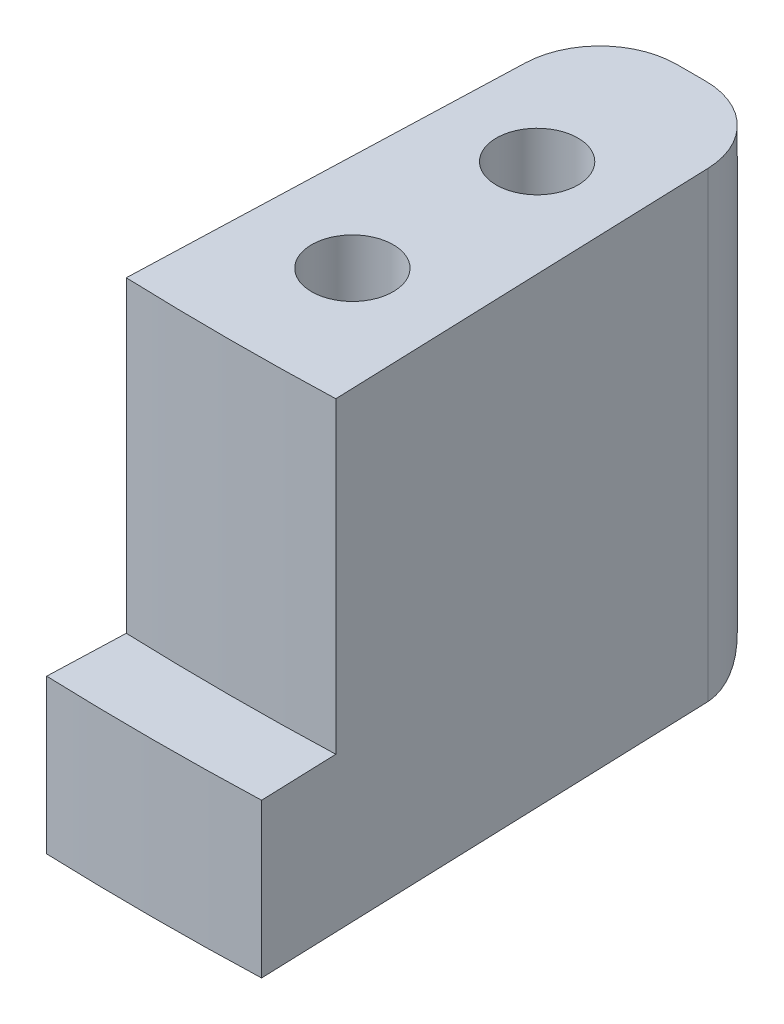
SolidWorks part; units mm, degrees
ref_plane "前视基准面" through (0, 0, 0) normal (0, 0, 1) x (1, 0, 0)
ref_plane "上视基准面" through (0, 0, 0) normal (0, 1, 0) x (1, 0, 0)
ref_plane "右视基准面" through (0, 0, 0) normal (1, 0, 0) x (0, 0, -1)
ref_axis "顶盖中心轴" through (0, -55, 0) along (0, 1, 0)
sketch "草图1" plane through (0, 0, 0) normal (0, 1, 0) x (1, 0, 0)
  line L0 (-5.9355, -169.97) -> (-6.0728, -173.9021) construction
  line L1 (0, 0) -> (0, -125.794) construction
  line L3 (-5.7619, -165) -> (5.7619, -165)
  line L4 (-5.7619, -165) -> (-6.9799, -199.8782)
  line L5 (5.7619, -165) -> (6.9799, -199.8782)
  arc A0 (-6.8054, -194.8812) -> (6.8054, -194.8812) centre (0, 0) ccw
  arc A1 (-6.9799, -199.8782) -> (6.9799, -199.8782) centre (0, 0) ccw
  dimension "D1" = 2
  dimension "D2" = 195
  dimension "D4" = 200
  dimension "D3" = 165
extrude "主体" add sketch "草图1" along normal blind 30 contours L4 A0 L5 L3 region at (0, 0, 180.3958)
extrude "插销" add sketch "草图1<3>" along normal blind 10 contours L4 A1 L5 A0 region at (0, 0, 197.4704)
sketch "草图1<3>" plane through (0, 0, 0) normal (0, 1, 0) x (1, 0, 0) same geometry as "草图1"
ref_plane "对称面" through (0, 0, 0) normal (1, 0, 0) x (0, 0, -1)
fillet "圆角1" radius 5 3 edges at (-5.7619, 15, 165) (5.7619, 15, 165) (0, 0, 165)
hole_wizard "M5 间隙孔1" positions "草图4" profile "草图5" hole size "M5" standard "ISO" end condition up to next
sketch "草图4" plane through (0, 30, 0) normal (0, 1, 0) x (1, 0, 0)
  line L0 (0, -13.75) -> (0, 13.75) construction
  point P0 (0, -187)
  point P2 (0, -175)
  dimension "D1" = 175
  dimension "D2" = 187
sketch "草图5" plane through (0, 30, 187) normal (1, 0, 0) x (0, 0, 1)
  line L0 (0, 0) -> (0, 30)
  line L1 (0, 30) -> (2.65, 30)
  line L2 (2.65, 30) -> (2.65, 0)
  line L5 (2.65, 0) -> (0, 0)
  line L11 (0, -6.35) -> (0, 107.95) construction
  dimension "通孔孔直径" = 5.3
  dimension "通孔孔深度" = 30
sketch "草图6" plane through (0, 0, 0) normal (0, -1, 0) x (1, 0, 0)
  line L1 (-4.792, 175) -> (-2.396, 170.85)
  line L2 (-2.396, 170.85) -> (2.396, 170.85)
  line L3 (2.396, 170.85) -> (4.792, 175)
  line L4 (4.792, 175) -> (2.396, 179.15)
  line L5 (2.396, 179.15) -> (-2.396, 179.15)
  line L6 (-2.396, 179.15) -> (-4.792, 175)
  line L7 (-4.792, 187) -> (-2.396, 182.85)
  line L8 (-2.396, 182.85) -> (2.396, 182.85)
  line L9 (2.396, 182.85) -> (4.792, 187)
  line L10 (4.792, 187) -> (2.396, 191.15)
  line L11 (2.396, 191.15) -> (-2.396, 191.15)
  line L12 (-2.396, 191.15) -> (-4.792, 187)
  circle A0 centre (0, 175) radius 4.15 construction
  circle A1 centre (0, 187) radius 4.15 construction
  dimension "D1" = 8.3
  dimension "D2" = 8.3
extrude "切除-拉伸1" cut sketch "草图6" against normal blind 5
